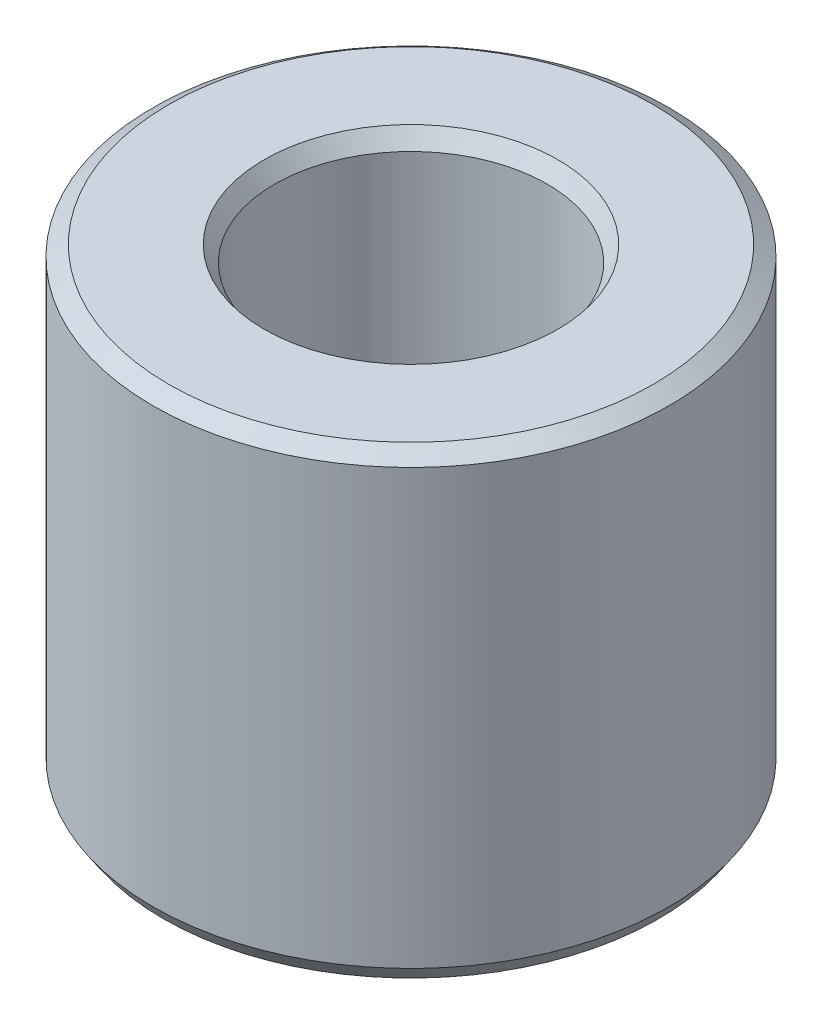
SolidWorks part; units mm, degrees
ref_plane "Front Plane" through (0, 0, 0) normal (0, 0, 1) x (1, 0, 0)
ref_plane "Top Plane" through (0, 0, 0) normal (0, 1, 0) x (1, 0, 0)
ref_plane "Right Plane" through (0, 0, 0) normal (1, 0, 0) x (0, 0, -1)
sketch "Sketch1" plane through (0, 0, 0) normal (0, 1, 0) x (1, 0, 0)
  circle A0 centre (0, 0) radius 45
  dimension "SLEEVE_OD" = 90
extrude "Boss-Extrude1" add sketch "Sketch1" along normal blind 80.2457
sketch "Sketch2" plane through (0, 0, 0) normal (0, 1, 0) x (1, 0, 0)
  circle A0 centre (0, 0) radius 23.7589
  dimension "BORE_D" = 47.5177
extrude "Cut-Extrude1" cut sketch "Sketch2" along normal through all
chamfer "Chamfer1" distance 1.8513 angle 56.151 4 edges at (0, 80.2457, 23.7589) (0, 0, 23.7589) (0, 0, 45) (0, 80.2457, 45) first distance on face at (0, 80.2457, 23.7589) first distance on face at (0, 0, 23.7589) first distance on face at (0, 80.2457, 45)
